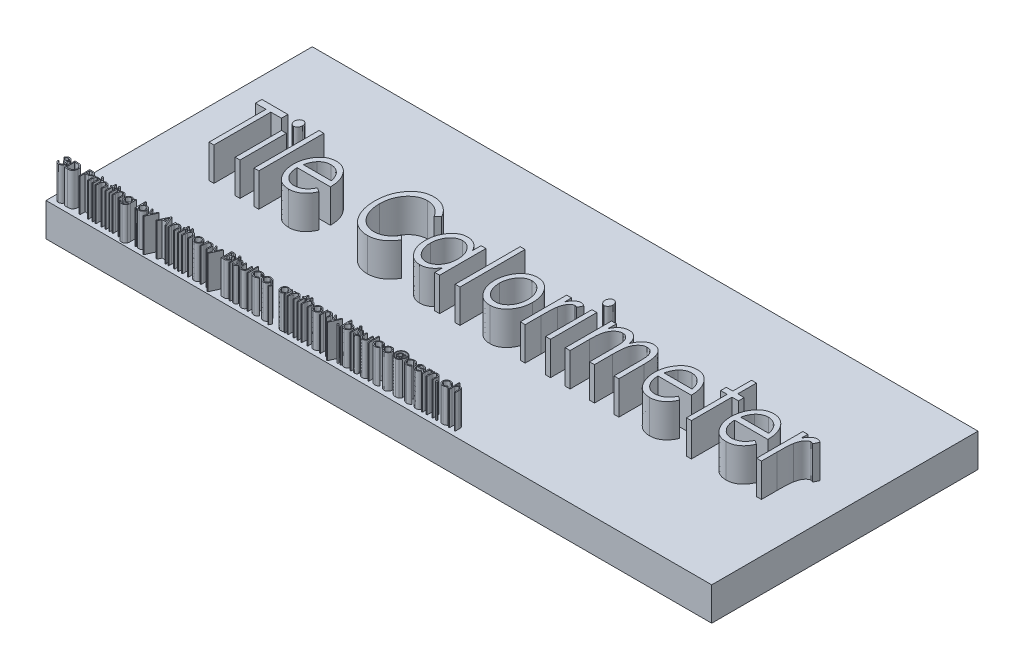
SolidWorks part; units mm, degrees
ref_plane "Front Plane" through (0, 0, 0) normal (0, 0, 1) x (1, 0, 0)
ref_plane "Top Plane" through (0, 0, 0) normal (0, 1, 0) x (1, 0, 0)
ref_plane "Right Plane" through (0, 0, 0) normal (1, 0, 0) x (0, 0, -1)
sketch "Sketch1" plane through (0, 0, 0) normal (0, 1, 0) x (1, 0, 0)
  line L1 (-100, 40) -> (100, 40)
  line L2 (-100, 40) -> (-100, -40)
  line L3 (-100, -40) -> (100, -40)
  line L4 (100, 40) -> (100, -40)
  dimension "D1" = 200
  dimension "D2" = 80
  dimension "D3" = 40
  dimension "D4" = 100
extrude "Boss-Extrude1" add sketch "Sketch1" along normal blind 10
sketch "Sketch2" plane through (0, 10, 0) normal (0, 1, 0) x (1, 0, 0)
  text T0 "Tile Calorimeter" font "Century Gothic" height in points 72
extrude "Boss-Extrude2" add sketch "Sketch2" along normal blind 10
sketch "Sketch3" plane through (0, 10, 0) normal (0, 1, 0) x (1, 0, 0)
  text T0 "3D Printing by Anthony Bisulco, anthony.bisulco@cern.ch"
extrude "Boss-Extrude3" add sketch "Sketch3" along normal blind 10
sketch "Sketch4" plane through (0, 10, 0) normal (0, 1, 0) x (1, 0, 0)
  line L0 (-1181.6917, 497.6108) -> (183.6416, 497.6108) construction
  line L1 (379.4521, 495.3593) -> (1744.7855, 495.3593) construction
  line L2 (50.5304, -20.8504) -> (54.6336, -23.9178)
  line L3 (50.7495, -30.3714) -> (51.1279, -34.116)
  line L4 (51.1279, -34.116) -> (49.9727, -31.3075)
  line L5 (49.9727, -31.3075) -> (47.0247, -33.4189)
  line L6 (47.0247, -33.4189) -> (49.2158, -30.2519)
  line L7 (49.2158, -30.2519) -> (47.1841, -23.1609)
  line L8 (47.1841, -23.1609) -> (50.5304, -20.8504)
  line L9 (76.9422, -24.8141) -> (78.5356, -25.9893)
  line L10 (78.5356, -25.9893) -> (76.6434, -25.9694)
  line L11 (78.7747, -30.0527) -> (75.0898, -30.212)
  line L12 (75.3089, -25.6905) -> (76.9422, -24.8141)
  line L13 (59.0953, -30.949) -> (56.5457, -29.495)
  line L14 (56.5457, -29.495) -> (54.3945, -30.6104)
  line L15 (54.3945, -30.6104) -> (56.4063, -24.8938)
  line L16 (73.556, -30.949) -> (70.9666, -29.495)
  line L17 (70.9666, -29.495) -> (68.8354, -30.6303)
  line L18 (68.8354, -30.6303) -> (70.8471, -24.8938)
  line L19 (59.3144, -24.9137) -> (63.8757, -24.9336)
  line L20 (63.8757, -24.9336) -> (63.8558, -25.9694)
  line L21 (63.8558, -25.9694) -> (62.2225, -25.9893)
  line L22 (62.2225, -25.9893) -> (62.2026, -30.949)
  line L23 (62.2026, -30.949) -> (60.9676, -30.9291)
  line L24 (60.9676, -30.9291) -> (60.9278, -25.9694)
  line L25 (60.9278, -25.9694) -> (59.3144, -25.9495)
  line L26 (59.3144, -25.9495) -> (59.3144, -24.9137)
  line L27 (64.6724, -24.9137) -> (65.9273, -24.9336)
  line L28 (65.9273, -24.9336) -> (65.9472, -29.8933)
  line L29 (65.9472, -29.8933) -> (68.3773, -29.9132)
  line L30 (68.3773, -29.9132) -> (68.3573, -30.949)
  line L31 (68.3573, -30.949) -> (64.6724, -30.9291)
  line L32 (64.6724, -30.9291) -> (64.6724, -24.9137)
  line L33 (56.5059, -31.9051) -> (58.2388, -31.9848)
  line L34 (58.2388, -31.9848) -> (57.6014, -33.5384)
  line L35 (56.7648, -33.6579) -> (56.5059, -31.9051)
  line L36 (67.3614, -31.925) -> (67.3415, -34.116)
  line L37 (67.0228, -34.0961) -> (67.0228, -31.9051)
  line L38 (77.3804, -31.9051) -> (79.0535, -31.925)
  line L39 (78.3962, -32.2238) -> (78.3763, -34.116)
  line L40 (78.0377, -34.0961) -> (78.0178, -32.2039)
  ellipse E0 centre (54.912, -32.9525) end of major axis (56.1873, -32.8997) minor radius 0.6693
  ellipse E1 centre (59.7527, -32.8422) end of major axis (60.7397, -33.4471) minor radius 0.8618
  ellipse E2 centre (62.5407, -32.9516) end of major axis (63.8324, -32.9003) minor radius 0.6639
  ellipse E3 centre (65.0328, -32.9143) end of major axis (66.0577, -32.737) minor radius 0.6757
  ellipse E4 centre (69.6953, -32.9294) end of major axis (70.6578, -32.8284) minor radius 0.8476
  ellipse E5 centre (72.8386, -32.9525) end of major axis (74.1139, -32.8997) minor radius 0.6693
  ellipse E6 centre (75.5075, -32.9817) end of major axis (76.3454, -32.886) minor radius 0.6262
  spline S0 degree 3 poles (54.6336, -23.9178) (53.7572, -25.5976) (52.9813, -27.3338) (52.0043, -28.9572) (51.6794, -29.4971) (51.1678, -29.9) (50.7495, -30.3714) knots 0 0 0 0 1 1 1 2 2 2 2
  spline S1 degree 3 poles (76.6434, -25.9694) (77.1988, -27.4007) (77.9975, -28.7286) (78.7747, -30.0527) knots 0 0 0 0 1 1 1 1
  spline S2 degree 3 poles (75.0898, -30.212) (75.3089, -30.0792) (75.4938, -29.8523) (75.7471, -29.8136) (76.3051, -29.7285) (76.8758, -29.8402) (77.4401, -29.8535) knots 0 0 0 0 1 1 1 2 2 2 2
  spline S3 degree 3 poles (77.4401, -29.8535) (76.8834, -28.3974) (76.0854, -27.0423) (75.3089, -25.6905) knots 0 0 0 0 1 1 1 1
  spline S4 degree 3 poles (56.4063, -24.8938) (57.0769, -25.3254) (58.0944, -25.4597) (58.4181, -26.1885) (59.0686, -27.6534) (58.8695, -29.3622) (59.0953, -30.949) knots 0 0 0 0 1 1 1 2 2 2 2
  spline S5 degree 3 poles (70.8471, -24.8938) (71.5244, -25.332) (72.5494, -25.4721) (72.8788, -26.2084) (73.5307, -27.6655) (73.3303, -29.3688) (73.556, -30.949) knots 0 0 0 0 1 1 1 2 2 2 2
